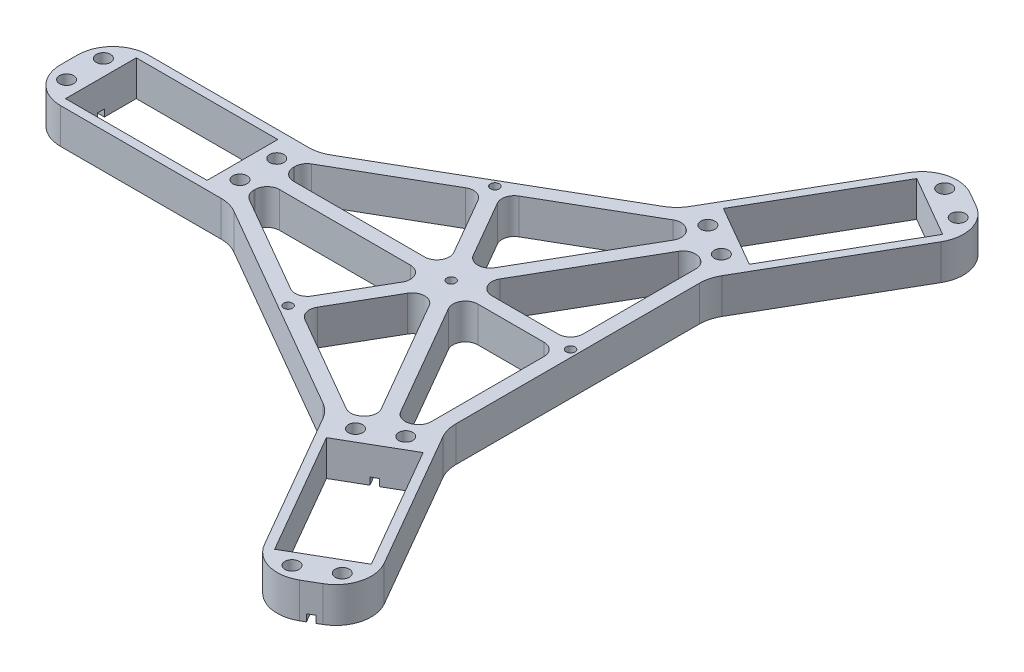
SolidWorks part; units mm, degrees
ref_plane "Front Plane" through (0, 0, 0) normal (0, 0, 1) x (1, 0, 0)
ref_plane "Top Plane" through (0, 0, 0) normal (0, 1, 0) x (1, 0, 0)
ref_plane "Right Plane" through (0, 0, 0) normal (1, 0, 0) x (0, 0, -1)
sketch "Sketch1" plane through (0, 0, 0) normal (0, 1, 0) x (1, 0, 0)
  line L0 (0, 10) -> (40, 10) construction
  line L1 (0, 0) -> (40, 0)
  line L2 (0, 0) -> (0, 20)
  line L3 (0, 20) -> (40, 20)
  line L4 (40, 0) -> (40, 20)
  line L5 (0, 20) -> (-4.5, 20)
  line L6 (-9, -2.4) -> (49, -2.4)
  line L7 (-9, -2.4) -> (-9, 22.4)
  line L8 (-9, 22.4) -> (49, 22.4)
  line L9 (49, -2.4) -> (49, 22.4)
  line L10 (-9, -2.4) -> (49, 22.4) construction
  line L11 (-9, 22.4) -> (49, -2.4) construction
  line L12 (-4.5, 20) -> (-4.5, 15.2)
  line L13 (20, 20) -> (20, 0) construction
  line L14 (49, 10) -> (130.7387, 10)
  line L15 (139.8397, 100.7365) -> (119.8397, 66.0955)
  line L16 (139.8397, 100.7365) -> (157.1603, 90.7365)
  line L17 (157.1603, 90.7365) -> (137.1603, 56.0955)
  line L18 (119.8397, 66.0955) -> (137.1603, 56.0955)
  line L19 (157.1603, 90.7365) -> (159.4103, 94.6336)
  line L20 (142.2613, 109.7307) -> (113.2613, 59.5013)
  line L21 (142.2613, 109.7307) -> (163.7387, 97.3307)
  line L22 (163.7387, 97.3307) -> (134.7387, 47.1013)
  line L23 (113.2613, 59.5013) -> (134.7387, 47.1013)
  line L24 (159.4103, 94.6336) -> (155.2533, 97.0336)
  line L25 (124, 53.3013) -> (83.1306, -17.4865)
  line L26 (148.5, 95.7365) -> (128.5, 61.0955) construction
  line L27 (142.2613, 109.7307) -> (134.7387, 47.1013) construction
  line L28 (163.7387, 97.3307) -> (113.2613, 59.5013) construction
  line L29 (147.1603, 73.416) -> (129.8397, 83.416) construction
  line L30 (157.1603, -70.7365) -> (137.1603, -36.0955)
  line L31 (157.1603, -70.7365) -> (139.8397, -80.7365)
  line L32 (139.8397, -80.7365) -> (119.8397, -46.0955)
  line L33 (137.1603, -36.0955) -> (119.8397, -46.0955)
  line L34 (139.8397, -80.7365) -> (142.0897, -84.6336)
  line L35 (163.7387, -77.3307) -> (134.7387, -27.1013)
  line L36 (163.7387, -77.3307) -> (142.2613, -89.7307)
  line L37 (142.2613, -89.7307) -> (113.2613, -39.5013)
  line L38 (134.7387, -27.1013) -> (113.2613, -39.5013)
  line L39 (142.0897, -84.6336) -> (146.2467, -82.2336)
  line L40 (124, -33.3013) -> (83.1306, 37.4865)
  line L41 (148.5, -75.7365) -> (128.5, -41.0955) construction
  line L42 (163.7387, -77.3307) -> (113.2613, -39.5013) construction
  line L43 (142.2613, -89.7307) -> (134.7387, -27.1013) construction
  line L44 (129.8397, -63.416) -> (147.1603, -53.416) construction
  line L45 (49, 22.4) -> (113.2613, 59.5013)
  line L46 (134.7387, 47.1013) -> (134.7387, -27.1013)
  line L47 (113.2613, -39.5013) -> (49, -2.4)
  line L48 (49, 17.7812) -> (117.2613, 57.1919)
  line L49 (130.7387, 49.4107) -> (130.7387, -29.4107)
  line L50 (117.2613, -37.1919) -> (49, 2.2188)
  line L51 (51, 18.9359) -> (115.2613, 56.0372) construction
  line L52 (130.7387, 47.1013) -> (130.7387, -27.1013) construction
  line L53 (115.2613, -36.0372) -> (51, 1.0641) construction
  line L54 (122.2679, 54.3013) -> (81.3986, -16.4865)
  line L55 (49, 8) -> (130.7387, 8)
  line L56 (125.7321, -32.3013) -> (84.8627, 38.4865)
  line L57 (125.7321, 52.3013) -> (84.8627, -18.4865)
  line L58 (49, 12) -> (130.7387, 12)
  line L59 (122.2679, -34.3013) -> (81.3986, 36.4865)
  line L60 (49, 12) -> (99, 12) construction
  line L61 (125.7321, -32.3013) -> (100.7321, 11) construction
  line L62 (122.2679, 54.3013) -> (97.2679, 11) construction
  line L63 (122.2679, -34.3013) -> (97.2679, 9) construction
  line L64 (124, 53.3013) -> (99, 10) construction
  line L65 (125.7321, 52.3013) -> (100.7321, 9) construction
  line L66 (124, -33.3013) -> (99, 10) construction
  line L67 (49, 10) -> (99, 10) construction
  line L68 (49, 8) -> (99, 8) construction
  line L69 (83.1306, 37.4865) -> (81.1306, 40.9506) construction
  line L70 (130.7387, 10) -> (134.7387, 10) construction
  line L71 (83.1306, -17.4865) -> (81.1306, -20.9506) construction
  circle A0 centre (-4.5, 15.2) radius 2
  circle A1 centre (44.5, 15.2) radius 2
  circle A2 centre (44.5, 4.8) radius 2
  circle A3 centre (-4.5, 4.8) radius 2
  circle A4 centre (155.2533, 97.0336) radius 2
  circle A5 centre (130.7533, 54.5984) radius 2
  circle A6 centre (121.7467, 59.7984) radius 2
  circle A7 centre (146.2467, 102.2336) radius 2
  circle A8 centre (146.2467, -82.2336) radius 2
  circle A9 centre (121.7467, -39.7984) radius 2
  circle A10 centre (130.7533, -34.5984) radius 2
  circle A11 centre (155.2533, -77.0336) radius 2
  circle A12 centre (82.1306, -19.2186) radius 1.25
  circle A13 centre (82.1306, 39.2186) radius 1.25
  circle A14 centre (132.7387, 10) radius 1.25
  circle A15 centre (99, 10) radius 1.25
  point P7 (20, 10)
  point P34 (138.5, 78.416)
  point P57 (138.5, -58.416)
  point P74 (99, 10)
  dimension "D7" = 4
  dimension "D1" = 40
  dimension "D2" = 20
  dimension "D3" = 58
  dimension "D4" = 24.8
  dimension "D5" = 4.5
  dimension "D6" = 4.8
  dimension "D10" = 4
  dimension "D11" = 4
  dimension "D12" = 4
  dimension "D13" = 2
  dimension "D14" = 2
  dimension "D9" = 3
extrude "Boss-Extrude1" add sketch "Sketch1" along normal blind 10 contours L9 L55 L54 L14 | L14 L59 L58 L9 | L55 L54 L50 L25 | L57 L59 L25 L50 | L38 L50 L9 L47 | L59 L25 L14 | L55 L59 L54 | L40 L54 L14 | L58 L40 L25 | L54 L58 L56 | L58 L56 L57 | L14 L56 L25 | L57 L14 L40 | L25 L55 L40 | L59 L57 L55 | L56 L57 L55 | L58 L57 L14 L49 | L56 L55 L49 L14 | L38 L56 L55 L40 | L59 L38 L40 L57 | L59 L54 L58 | L59 L58 L40 L48 | L54 L56 L48 L40 | L56 L25 L23 L54 | L25 L58 L57 L23 | L23 L49 L38 L46 | L9 L48 L23 L45 | L6 L9 L8 L7 A1 A0 L3 L4 L1 L2 A2 A3 | L20 L23 L22 L21 A5 A4 L17 L18 L15 L16 A6 A7 | L35 L38 L37 L36 A9 A8 L32 L33 L30 L31 A10 A11 region at (-8.3692, 0, -10) region at (49.8, 0, 0.0906) region at (115.6635, 0, 39.0432) region at (81.1706, 0, -40.8814) region at (72.5578, 0, -9.0041) region at (89.4843, 0, 4.4949) region at (128.4579, 0, -84.2138) region at (72.5578, 0, -10.9959) region at (96.6906, 0, -8.6667) region at (91.2048, 0, 5.4883) region at (111.3586, 0, 13.3976) region at (89.4843, 0, -24.4949) region at (97.5899, 0, -10.8141) region at (96.6906, 0, -11.3333) region at (97.5899, 0, -9.1859) region at (99, 0, -8.3718) region at (99, 0, -7.3333) region at (132.3441, 0, 27.5725) region at (113.0836, 0, 12.4017) region at (91.2048, 0, -25.4883) region at (111.3586, 0, -33.3976) region at (99, 0, -11.6282) region at (99, 0, -12.6667) region at (101.3094, 0, -8.6667) region at (100.4101, 0, -9.1859) region at (113.0836, 0, -32.4017) region at (100.4101, 0, -10.8141) region at (101.3094, 0, -11.3333) region at (116.3108, 0, -9.0067) region at (116.3108, 0, -10.9933)
sketch "Sketch2" plane through (-9, 0, 0) normal (-1, 0, 0) x (0, 0, 1)
  line L0 (2.4, 0) -> (-22.4, 0) construction
  line L1 (-11, -2) -> (-9, -2)
  line L2 (-11, -2) -> (-11, 2)
  line L3 (-11, 2) -> (-9, 2)
  line L4 (-9, -2) -> (-9, 2)
  line L5 (-11, -2) -> (-9, 2) construction
  line L6 (-11, 2) -> (-9, -2) construction
  point P0 (-10, 0)
  dimension "D1" = 2
  dimension "D2" = 4
extrude "Cut-Extrude1" cut sketch "Sketch2" against normal blind 56
sketch "Sketch3" plane through (74.4199, 0, 128.899) normal (0.5, 0, 0.866) x (0.866, 0, -0.5)
  line L0 (103.1365, 0) -> (78.3365, 0) construction
  line L1 (89.7365, -2) -> (91.7365, -2)
  line L2 (89.7365, -2) -> (89.7365, 2)
  line L3 (89.7365, 2) -> (91.7365, 2)
  line L4 (91.7365, -2) -> (91.7365, 2)
  line L5 (89.7365, -2) -> (91.7365, 2) construction
  line L6 (89.7365, 2) -> (91.7365, -2) construction
  point P0 (90.7365, 0)
  dimension "D1" = 2
  dimension "D2" = 4
extrude "Cut-Extrude2" cut sketch "Sketch3" against normal blind 56
sketch "Sketch4" plane through (83.0801, 0, -143.899) normal (0.5, 0, -0.866) x (-0.866, 0, -0.5)
  line L0 (-68.3365, 0) -> (-93.1365, 0) construction
  line L1 (-81.7365, -2) -> (-79.7365, -2)
  line L2 (-81.7365, -2) -> (-81.7365, 2)
  line L3 (-81.7365, 2) -> (-79.7365, 2)
  line L4 (-79.7365, -2) -> (-79.7365, 2)
  line L5 (-81.7365, -2) -> (-79.7365, 2) construction
  line L6 (-81.7365, 2) -> (-79.7365, -2) construction
  point P0 (-80.7365, 0)
  dimension "D1" = 2
  dimension "D2" = 4
extrude "Cut-Extrude3" cut sketch "Sketch4" against normal blind 56
fillet "Fillet1" radius 10 12 edges at (113.2613, 5, 39.5013) (134.7387, 5, 27.1013) (134.7387, 5, -47.1013) (113.2613, 5, -59.5013) (49, 5, -22.4) (49, 5, 2.4) (142.2613, 5, -109.7307) (163.7387, 5, -97.3307) (163.7387, 5, 77.3307) (142.2613, 5, 89.7307) (-9, 5, -22.4) (-9, 5, 2.4)
fillet "Fillet2" radius 3.5 24 edges at (84.8627, 5, -38.4865) (122.2679, 5, -54.3013) (117.2613, 5, -57.1919) (125.7321, 5, -52.3013) (130.7387, 5, -49.4107) (130.7387, 5, -12) (130.7387, 5, -8) (130.7387, 5, 29.4107) (125.7321, 5, 32.3013) (122.2679, 5, 34.3013) (117.2613, 5, 37.1919) (84.8627, 5, 18.4865) (81.3986, 5, 16.4865) (49, 5, -8) (49, 5, -2.2188) (49, 5, -12) (49, 5, -17.7812) (95.5359, 5, -8) (99, 5, -6) (102.4641, 5, -8) (102.4641, 5, -12) (99, 5, -14) (95.5359, 5, -12) (81.3986, 5, -36.4865)
